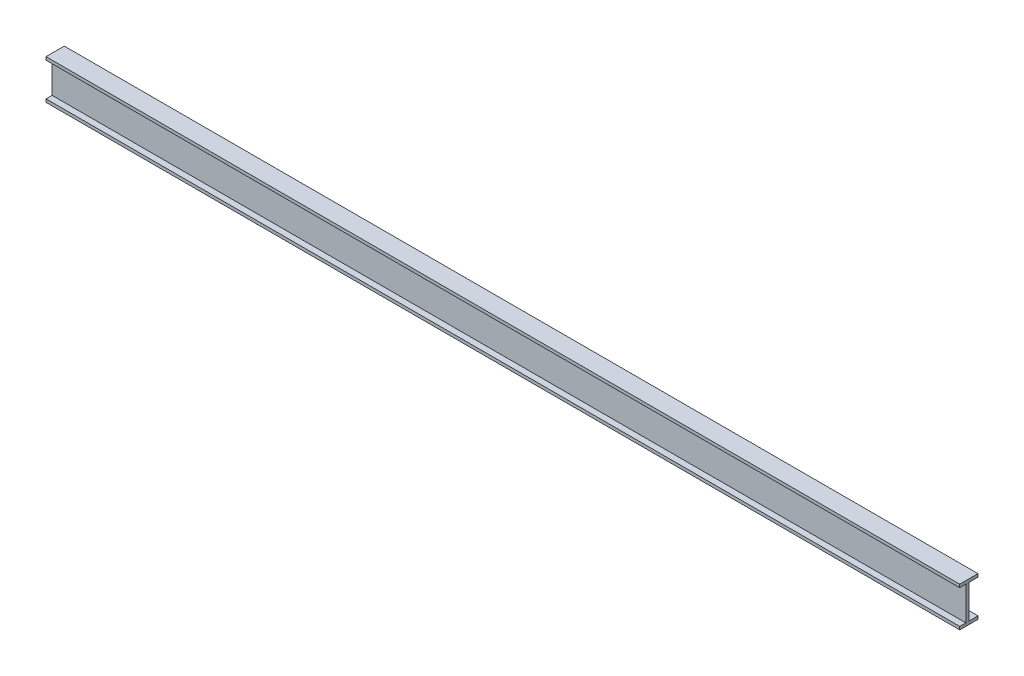
SolidWorks part; units mm, degrees
ref_plane "Спереди" through (0, 0, 0) normal (0, 0, 1) x (1, 0, 0)
ref_plane "Сверху" through (0, 0, 0) normal (0, 1, 0) x (1, 0, 0)
ref_plane "Справа" through (0, 0, 0) normal (1, 0, 0) x (0, 0, -1)
sketch "Эскиз1" plane through (0, 0, 0) normal (1, 0, 0) x (0, 0, -1)
  line L0 (-30, 0) -> (30, 0)
  line L1 (0, 0) -> (0, 120)
  line L2 (-30, 120) -> (30, 120)
extrude "Вытянуть-Тонкостенный1" add sketch "Эскиз1" along normal blind 3000 thin thin type one direction reverse wall 10
